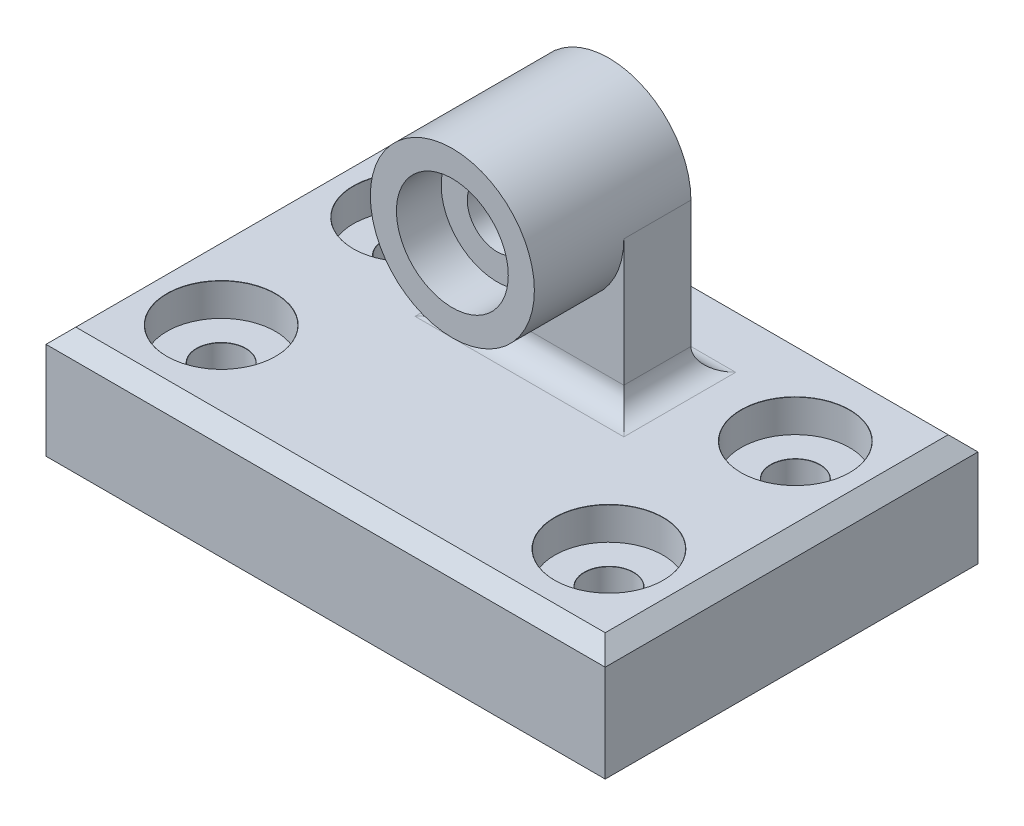
SolidWorks part; units mm, degrees
material "Brass"
ref_plane "Front Plane" through (0, 0, 0) normal (0, 0, 1) x (1, 0, 0)
ref_plane "Top Plane" through (0, 0, 0) normal (0, 1, 0) x (1, 0, 0)
ref_plane "Right Plane" through (0, 0, 0) normal (1, 0, 0) x (0, 0, -1)
sketch "Sketch1" plane through (0, 0, 0) normal (0, 1, 0) x (1, 0, 0)
  line L1 (0, 0) -> (75, 0)
  line L2 (0, 0) -> (0, 50)
  line L3 (0, 50) -> (75, 50)
  line L4 (75, 0) -> (75, 50)
  dimension "D1" = 50
  dimension "Sketch 1" = 75
extrude "Boss-Extrude1" add sketch "Sketch1" along normal blind 15 contours L2 L1 L4 L3
chamfer "Chamfer1" distance 2 angle 45 4 edges at (75, 15, -25) (37.5, 15, -50) (0, 15, -25) (37.5, 15, 0)
sketch "Sketch2" plane through (0, 15, 0) normal (0, 1, 0) x (1, 0, 0)
  line L0 (0, 25) -> (75, 25) construction
  line L3 (0, 0) -> (0, 50) construction
  line L4 (75, 50) -> (75, 0) construction
  line L5 (37.5, 50) -> (37.5, 38) construction
  line L6 (0, 50) -> (75, 50) construction
  line L7 (26.5, 38) -> (48.5, 38)
  line L8 (48.5, 38) -> (48.5, 29)
  line L9 (48.5, 29) -> (26.5, 29)
  line L10 (26.5, 29) -> (26.5, 38)
  point P13 (37.5, 38)
  dimension "D1" = 12
  dimension "D2" = 22
  dimension "D3" = 9
extrude "Boss-Extrude2" add sketch "Sketch2" along normal blind 20 contours L10 L7 L8 L9
sketch "Sketch3" plane through (0, 0, -38) normal (0, 0, -1) x (-1, 0, 0)
  line L0 (-26.5, 35) -> (-48.5, 35) construction
  circle A0 centre (-37.5, 35) radius 11
extrude "Boss-Extrude3" add sketch "Sketch3" against normal blind 21
sketch "Sketch4" plane through (0, 0, -17) normal (0, 0, 1) x (1, 0, 0)
  circle A0 centre (37.5, 35) radius 7.5
  circle A1 centre (37.5, 35) radius 4
  dimension "D1" = 8
  dimension "D2" = 15
extrude "Cut-Extrude2" cut sketch "Sketch4" against normal through all contours A1
extrude "Cut-Extrude3" cut sketch "Sketch4<4>" against normal blind 6
sketch "Sketch4<4>" plane through (0, 0, -17) normal (0, 0, 1) x (1, 0, 0) same geometry as "Sketch4"
fillet "Fillet1" radius 3 4 edges at (26.5, 15, -33.5) (37.5, 15, -38) (48.5, 15, -33.5) (37.5, 15, -29)
sketch "Sketch7" plane through (0, 15, 0) normal (0, 1, 0) x (1, 0, 0)
  line L0 (63.5, 50) -> (63.5, 37) construction
  line L1 (0, 50) -> (75, 50) construction
  line L2 (37.5, 50) -> (37.5, 0) construction
  line L3 (75, 0) -> (0, 0) construction
  line L4 (63.5, 37) -> (37.5, 37) construction
  circle A0 centre (63.5, 37) radius 3.3
  circle A1 centre (63.5, 37) radius 7.3
  dimension "D3" = 6.6
  dimension "D4" = 14.6
  dimension "D1" = 13
  dimension "D2" = 26
hole_wizard "CBORE for M6 Hex Head Bolt2" positions "3DSketch2" profile "Sketch10" counterbore size "M6" standard "ANSI Metric" end condition through all
sketch3d "3DSketch2"
  point P0 (63.5, 15, -37)
sketch "Sketch10" plane through (63.5, 15, -37) normal (1, 0, 0) x (0, 0, 1)
  line L0 (0, 0) -> (0, 15)
  line L1 (0, 15) -> (3.3, 15)
  line L3 (3.3, 4.405) -> (3.325, 4.38)
  line L4 (3.325, 4.38) -> (7.275, 4.38)
  line L5 (7.275, 4.38) -> (7.275, 0.025)
  line L6 (7.275, 0.025) -> (7.3, 0)
  line L7 (7.3, 0) -> (0, 0)
  line L8 (-7.275, 0.025) -> (-7.3, 0) construction
  line L9 (-3.3, 4.405) -> (-3.325, 4.38) construction
  line L10 (3.3, 15) -> (3.3, 4.405)
  line L11 (0, -6.35) -> (0, 107.95) construction
  dimension "Thru Hole Dia." = 6.6
  dimension "Thru Hole Depth" = 15
  dimension "C'Bore Dia." = 14.55
  dimension "C'Bore Depth" = 4.38
  dimension "Near C'Sink Dia." = 14.6
  dimension "Near C'Sink Angle" = 90
  dimension "Mid C'Sink Dia." = 6.65
  dimension "Mid C'Sink Angle" = 90
pattern_linear "LPattern2" count 2 spacing 52 along (-1, 0, 0) count 2 spacing 25 along (0, 0, 1) of "CBORE for M6 Hex Head Bolt2"
